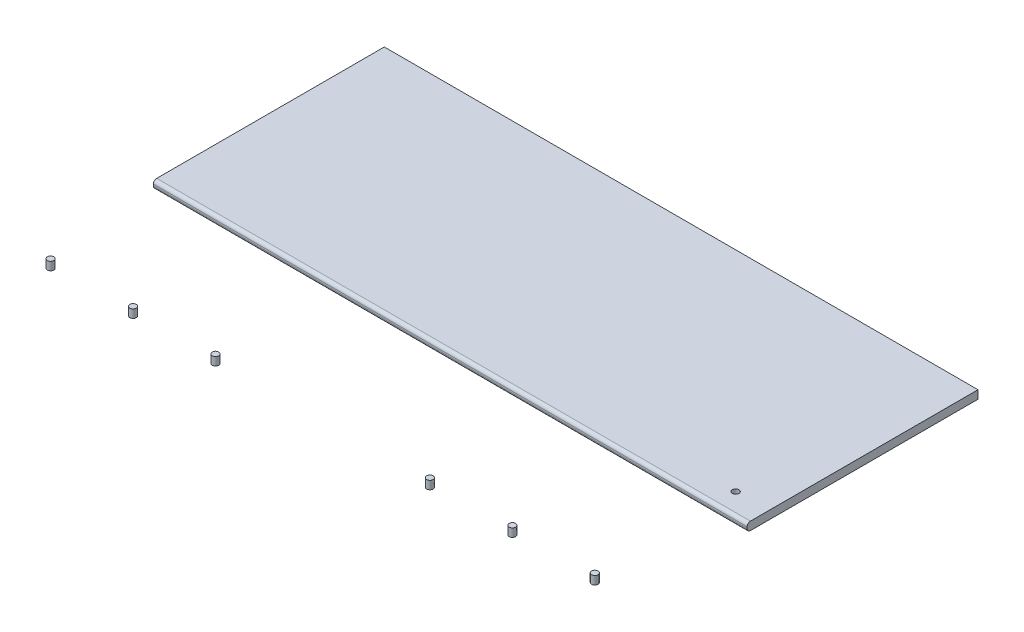
SolidWorks part; units mm, degrees
material "6061 Alloy"
ref_plane "Front Plane" through (0, 0, 0) normal (0, 0, 1) x (1, 0, 0)
ref_plane "Top Plane" through (0, 0, 0) normal (0, 1, 0) x (1, 0, 0)
ref_plane "Right Plane" through (0, 0, 0) normal (1, 0, 0) x (0, 0, -1)
sketch "Sketch1" plane through (0, 0, 0) normal (0, 1, 0) x (1, 0, 0)
  line L1 (-228.6, 88.9) -> (228.6, 88.9)
  line L2 (-228.6, 88.9) -> (-228.6, -88.9)
  line L3 (-228.6, -88.9) -> (228.6, -88.9)
  line L4 (228.6, 88.9) -> (228.6, -88.9)
  line L5 (-228.6, 88.9) -> (228.6, -88.9) construction
  line L6 (-228.6, -88.9) -> (228.6, 88.9) construction
  circle A10 centre (203.2, -180.7913) radius 2.5019 construction
  circle A11 centre (139.7, -180.7913) radius 2.5019 construction
  circle A12 centre (76.2, -180.7913) radius 2.5019 construction
  circle A13 centre (-88.9, -180.7913) radius 2.5019 construction
  circle A14 centre (-152.4, -180.7913) radius 2.5019 construction
  circle A15 centre (-215.9, -180.7913) radius 2.5019 construction
  circle A16 centre (203.2, -180.7913) radius 2.5019
  circle A17 centre (139.7, -180.7913) radius 2.5019
  circle A18 centre (76.2, -180.7913) radius 2.5019
  circle A19 centre (-88.9, -180.7913) radius 2.5019
  circle A20 centre (-152.4, -180.7913) radius 2.5019
  circle A21 centre (-215.9, -180.7913) radius 2.5019
  point P0 (0, 0)
  dimension "D1" = 177.8
  dimension "D2" = 457.2
extrude "Boss-Extrude1" add sketch "Sketch1" along normal blind 6.35
sketch "Sketch2" plane through (-228.6, 0, 0) normal (-1, 0, 0) x (0, 0, 1)
  line L0 (-88.9, 6.35) -> (88.9, 6.35) construction
  line L1 (88.9, 6.35) -> (88.9, 0) construction
  circle A0 centre (85.725, 3.175) radius 1.5875
  dimension "D1" = 3.175
  dimension "D2" = 3.175
  dimension "D3" = 3.175
extrude "Cut-Extrude1" [suppressed] cut sketch "Sketch2" against normal through all
fillet "Fillet1" radius 2.54 2 edges at (0, 0, 88.9) (0, 6.35, 88.9)
sketch "Sketch3" plane through (228.6, 0, 0) normal (1, 0, 0) x (0, 0, -1)
  line L0 (88.9, 6.35) -> (88.9, 0) construction
  line L1 (-48.26, 4.572) -> (-33.02, 4.572)
  line L2 (-48.26, 4.572) -> (-48.26, 1.27)
  line L3 (-48.26, 1.27) -> (-33.02, 1.27)
  line L4 (-33.02, 4.572) -> (-33.02, 1.27)
  line L5 (-48.26, 4.572) -> (-33.02, 1.27) construction
  line L6 (-48.26, 1.27) -> (-33.02, 4.572) construction
  line L7 (-86.36, 0) -> (88.9, 0) construction
  point P0 (-40.64, 2.921)
  dimension "D1" = 15.24
  dimension "D2" = 129.54
  dimension "D3" = 3.302
  dimension "D4" = 1.27
sketch "Sketch4" plane through (0, 0, 0) normal (0, -1, 0) x (1, 0, 0)
  line L0 (228.6, 86.36) -> (228.6, -88.9) construction
  line L2 (-228.6, 88.9) -> (228.6, 88.9) construction
  circle A1 centre (203.2, 72.3392) radius 2.54
  dimension "D2" = 5.08
  dimension "D1" = 16.5608
  dimension "D3" = 25.4
extrude "Cut-Extrude3" cut sketch "Sketch4" against normal through all
sketch "Sketch5" plane through (0, 0, 0) normal (0, -1, 0) x (1, 0, 0)
  line L0 (-228.6, 88.9) -> (228.6, 88.9) construction
  line L1 (-222.25, 61.1632) -> (-69.85, 61.1632)
  line L2 (-222.25, 61.1632) -> (-222.25, 88.9)
  line L3 (-222.25, 88.9) -> (-69.85, 88.9)
  line L4 (-69.85, 61.1632) -> (-69.85, 88.9)
  line L5 (-228.6, -88.9) -> (-228.6, 86.36) construction
  dimension "D1" = 6.35
  dimension "D2" = 152.4
  dimension "D3" = 27.7368
ref_axis "Axis1" through (0, 0, -88.9) along (0, 0.0143, 0.9999)
ref_plane "Plane1" through (0, 0, 0) normal (1, 0, 0) x (0, 0, -1)
